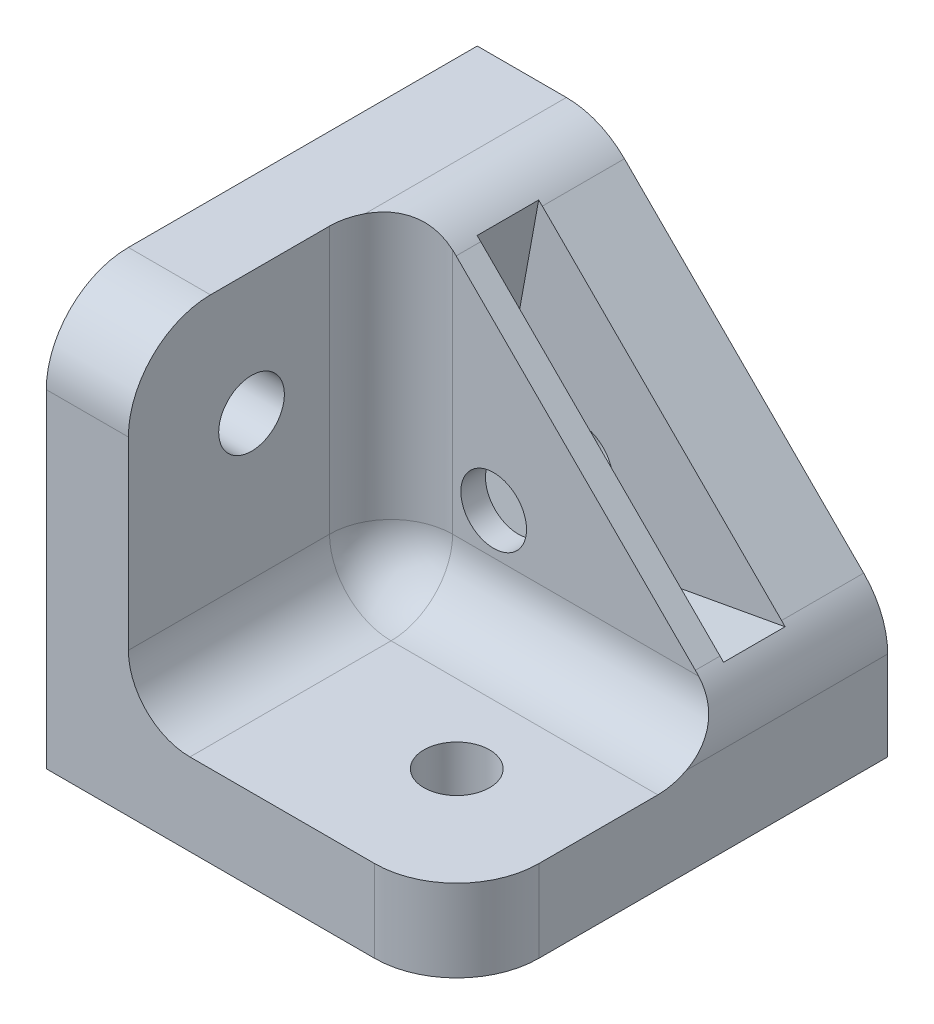
SolidWorks part; units mm, degrees
ref_plane "Front Plane" through (0, 0, 0) normal (0, 0, 1) x (1, 0, 0)
ref_plane "Top Plane" through (0, 0, 0) normal (0, 1, 0) x (1, 0, 0)
ref_plane "Right Plane" through (0, 0, 0) normal (1, 0, 0) x (0, 0, -1)
sketch "Sketch4" plane through (0, 0, 0) normal (0, 0, 1) x (1, 0, 0)
  line L2 (0, 0) -> (0, 20)
  line L3 (0, 20) -> (4, 20)
  line L4 (4, 4) -> (4, 20)
  line L5 (0, 0) -> (20, 0)
  line L7 (4, 4) -> (20, 4)
  line L8 (20, 0) -> (20, 4)
  line L9 (4, 20) -> (6, 20)
  line L10 (6, 20) -> (20, 6)
  line L11 (20, 6) -> (20, 4)
  dimension "D1" = 4
  dimension "D2" = 4
  dimension "D3" = 20
  dimension "D4" = 20
  dimension "D5" = 2
  dimension "D6" = 2
extrude "Boss-Extrude4" add sketch "Sketch4" along normal blind 8.2 separate body contours L5 L8 L7 L4 L3 L2 | L4 L7 region at (0.2828, 10, 0) region at (9.9325, 9.9325, 0)
extrude "Boss-Extrude5" add sketch "Sketch4<4>" along normal blind 21 contours L5 L8 L7 L4 L3 L2 region at (0.2828, 10, 0)
sketch "Sketch4<4>" plane through (0, 0, 0) normal (0, 0, 1) x (1, 0, 0) same geometry as "Sketch4"
hole_wizard "Ø3.2 (3.2) Diameter Hole1" positions "3DSketch2" profile "Sketch6" hole size "Ø3.2" standard "ANSI Metric" end condition through all
sketch3d "3DSketch2"
  line L0 (0, 0, 21) -> (0, 0, 0) construction
  line L1 (0, 0, 0) -> (20, 0, 0) construction
  line L2 (0, 0, 0) -> (0, 20, 0) construction
  point P0 (14, 0, 15)
  point P2 (0, 14, 15)
  point P4 (9, 9, 0)
  dimension "D1" = 14
  dimension "D2" = 14
  dimension "D3" = 15
  dimension "D4" = 15
  dimension "D5" = 9
  dimension "D6" = 9
sketch "Sketch6" plane through (14, 0, 15) normal (1, 0, 0) x (0, 0, -1)
  line L0 (0, 0) -> (0, 20)
  line L1 (0, 20) -> (1.6, 20)
  line L2 (1.6, 20) -> (1.6, 0)
  line L5 (1.6, 0) -> (0, 0)
  line L11 (0, -6.35) -> (0, 107.95) construction
  dimension "Thru Hole Dia." = 3.2
  dimension "Thru Hole Depth" = 20
fillet "Fillet1" radius 3 3 edges at (12, 4, 8.2) (4, 4, 14.6) (4, 12, 8.2)
fillet "Fillet2" radius 4 4 edges at (6, 20, 4.1858) (20, 6, 4.1858) (20, 2, 21) (2, 20, 21)
sketch "Sketch7" plane through (0, 0, 0) normal (0, 0, -1) x (-1, 0, 0)
  line L0 (-6.9932, 19.0068) -> (-4.9682, 7.9128)
  line L1 (-7.1716, 18.8284) -> (-18.8284, 7.1716) construction
  line L2 (-4.9682, 7.9128) -> (-7.9128, 4.9682)
  line L3 (-7.9128, 4.9682) -> (-19.0068, 6.9932)
  line L4 (-13, 13) -> (-6.4405, 6.4405) construction
  line L5 (-6.9932, 19.0068) -> (-19.0068, 6.9932)
extrude "Cut-Extrude2" cut sketch "Sketch7" against normal blind 3 from offset 4 offset against normal yes
equation "\"D2@Sketch4\"=\"D1@Sketch4\""
equation "\"D4@Sketch4\"=\"D3@Sketch4\""
equation "\"D6@Sketch4\"=\"D5@Sketch4\""
